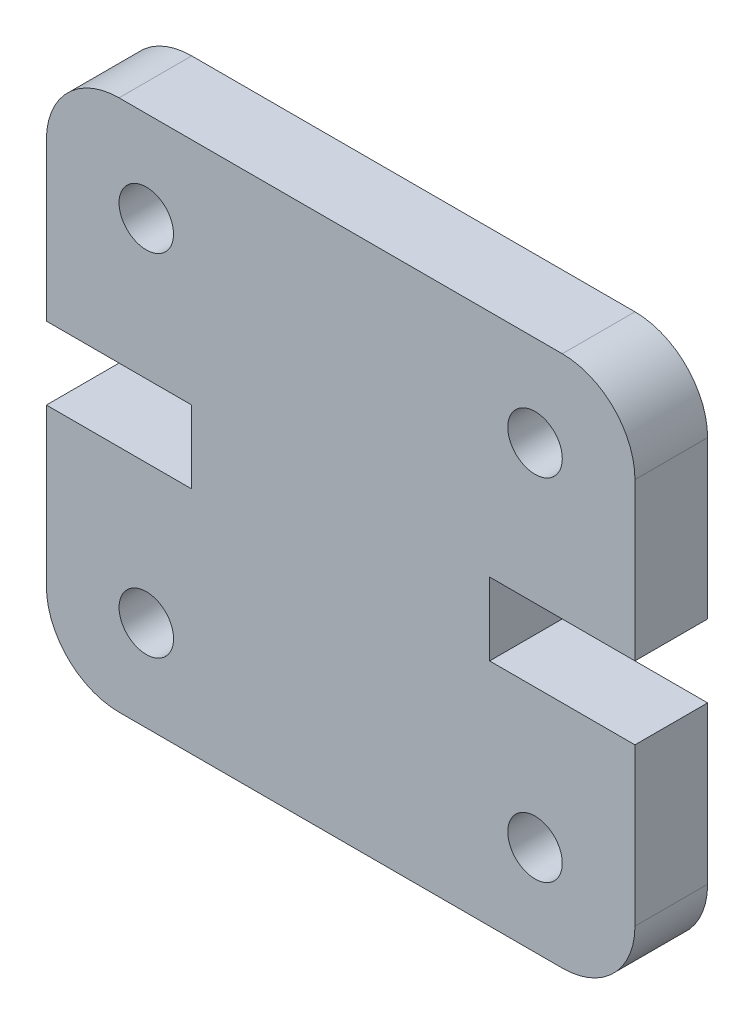
SolidWorks part; units mm, degrees
ref_plane "Front Plane" through (0, 0, 0) normal (0, 0, 1) x (1, 0, 0)
ref_plane "Top Plane" through (0, 0, 0) normal (0, 1, 0) x (1, 0, 0)
ref_plane "Right Plane" through (0, 0, 0) normal (1, 0, 0) x (0, 0, -1)
sketch "Sketch1" plane through (0, 0, 0) normal (0, 0, 1) x (1, 0, 0)
  line L0 (8.1, 14.645) -> (8.1, 0) construction
  line L1 (0, 7.3225) -> (16.2, 7.3225) construction
  line L2 (2, 14.645) -> (14.2, 14.645)
  line L3 (0, 8.3225) -> (4, 8.3225)
  line L4 (0, 8.3225) -> (0, 12.645)
  line L5 (12.2, 6.3225) -> (12.2, 8.3225)
  line L6 (16.2, 6.3225) -> (12.2, 6.3225)
  line L7 (16.2, 6.3225) -> (16.2, 2)
  line L8 (16.2, 8.3225) -> (16.2, 12.645)
  line L9 (16.2, 8.3225) -> (12.2, 8.3225)
  line L12 (0, 6.3225) -> (0, 2)
  line L17 (0, 6.3225) -> (4, 6.3225)
  line L18 (4, 6.3225) -> (4, 8.3225)
  line L19 (2, 0) -> (14.2, 0)
  circle A0 centre (2.75, 12.145) radius 0.75
  arc A1 (0, 12.645) -> (2, 14.645) centre (2, 12.645) cw
  circle A2 centre (13.45, 2.5) radius 0.75
  arc A3 (16.2, 2) -> (14.2, 0) centre (14.2, 2) cw
  arc A4 (16.2, 12.645) -> (14.2, 14.645) centre (14.2, 12.645) ccw
  circle A5 centre (13.45, 12.145) radius 0.75
  arc A11 (0, 2) -> (2, 0) centre (2, 2) ccw
  circle A13 centre (2.75, 2.5) radius 0.75
  point P9 (4, 7.3225)
  point P14 (8.1, 7.3225)
  point P27 (12.2, 7.3225)
  dimension "D1" = 1
  dimension "D2" = 2
  dimension "D8" = 1.5
  dimension "D3" = 2.75
  dimension "D4" = 8.1
  dimension "D5" = 2.5
  dimension "D6" = 6.3225
  dimension "D7" = 4
extrude "Boss-Extrude1" add sketch "Sketch1" along normal blind 4
sketch "Sketch2" plane through (0, 0, 0) normal (0, 0, -1) x (-1, 0, 0)
  line L0 (0, 0) -> (-16.2, 0)
  line L1 (-16.2, 0) -> (-16.2, 14.645)
  line L2 (-16.2, 14.645) -> (0, 14.645)
  line L3 (0, 14.645) -> (0, 0)
extrude "Cut-Extrude1" cut sketch "Sketch2" against normal blind 2
equation "\"D4@Sketch1\"= \"fingerWidth@parametersSketch@prostheticParameters.SLDPRT\" / 2'MIP width"
equation "\"D6@Sketch1\"=( \"HL@parametersSketch@prostheticParameters.SLDPRT\" * 0.117 - 4 - 3 - 2) / 2 'MIP length - Sil. Sht DIP - Sil. Sht MIP"
